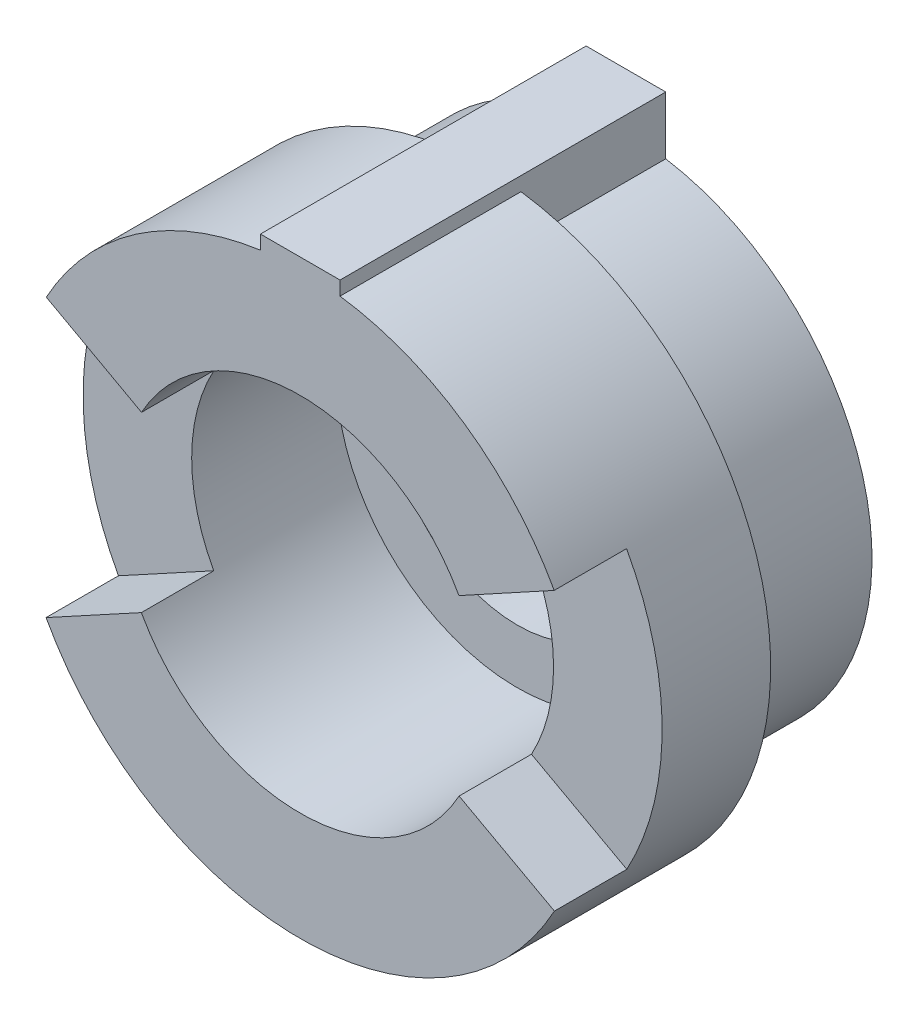
SolidWorks part; units mm, degrees
ref_plane "Front Plane" through (0, 0, 0) normal (0, 0, 1) x (1, 0, 0)
ref_plane "Top Plane" through (0, 0, 0) normal (0, 1, 0) x (1, 0, 0)
ref_plane "Right Plane" through (0, 0, 0) normal (1, 0, 0) x (0, 0, -1)
sketch "Sketch1" plane through (0, 0, 0) normal (0, 0, 1) x (1, 0, 0)
  circle A0 centre (0, 0) radius 8
  circle A1 centre (0, 0) radius 3.5
  dimension "D1" = 7
  dimension "D2" = 16
extrude "Boss-Extrude1" add sketch "Sketch1" along normal blind 3
sketch "Sketch2" plane through (0, 0, 3) normal (0, 0, 1) x (1, 0, 0)
  circle A0 centre (0, 0) radius 8
  circle A1 centre (0, 0) radius 5
  dimension "D1" = 16
  dimension "D2" = 10
extrude "Boss-Extrude2" add sketch "Sketch2" along normal blind 6
sketch "Sketch4" plane through (0, 0, 0) normal (0, 1, 0) x (1, 0, 0)
  line L0 (-8.56, -9) -> (-8.56, -7)
  line L1 (-16.56, -9) -> (-8.56, -9)
  line L2 (8.56, -9) -> (8.56, -7)
  line L3 (8.56, -9) -> (16.56, -9)
  line L4 (-16.56, -9) -> (-16.56, -7)
  line L5 (-16.56, -7) -> (-8.56, -7)
  line L6 (16.56, -9) -> (16.56, -7)
  line L7 (16.56, -7) -> (8.56, -7)
  dimension "D1" = 7
  dimension "D2" = 8.56
  dimension "D3" = 2
  dimension "D4" = 8.56
  dimension "D5" = 8
  dimension "D6" = 8
  dimension "D7" = 2
  dimension "D8" = 7
wrap "Wrap3" sketch "Sketch4" wrap type deboss source sketch "Sketch4" thickness 4 face at (8, 0, 0) parameters "D1"=4
sketch "Sketch5" plane through (0, 0, 0) normal (0, 0, -1) x (-1, 0, 0)
  line L0 (-1.1, 6.7104) -> (-1.1, 7.924)
  line L2 (1.1, 7.924) -> (1.1, 6.7104)
  arc A0 (-1.1, 7.924) -> (1.1, 7.924) centre (0, 0) ccw
  arc A1 (-1.1, 6.7104) -> (1.1, 6.7104) centre (0, 0) ccw
  circle A2 centre (0, 0) radius 8 construction
  dimension "D3" = 6.8
  dimension "D1" = 8
  dimension "D2" = 1.1
extrude "Cut-Extrude1" cut sketch "Sketch5" against normal blind 4
sketch "Sketch6" plane through (0, 0, 0) normal (0, 0, -1) x (-1, 0, 0)
  line L0 (-1.1, 7.7312) -> (-1.1, 8.3104)
  line L1 (-1.1, 8.3104) -> (1.1, 8.3104)
  line L2 (1.1, 8.3104) -> (1.1, 7.7312)
  line L3 (-1.1, 6.7104) -> (-1.1, 7.924) construction
  arc A0 (1.1, 7.7312) -> (-1.1, 7.7312) centre (0, -0.1929) ccw
  dimension "D1" = 8
  dimension "D2" = 1.1
  dimension "D3" = 1.0207
  dimension "D4" = 1.6
extrude "Boss-Extrude3" add sketch "Sketch6" against normal blind 9
equation "\"D3@Sketch5\"= 7 - \"tol1@parametersSketch@prostheticParameters.SLDPRT\" / 2"
equation "\"D2@Sketch5\"= 1.5 - \"tol2@parametersSketch@prostheticParameters.SLDPRT\""
equation "\"D2@Sketch6\"= 1.5 - \"tol2@parametersSketch@prostheticParameters.SLDPRT\""
equation "\"D4@Sketch6\"= 2 - \"tol2@parametersSketch@prostheticParameters.SLDPRT\""
